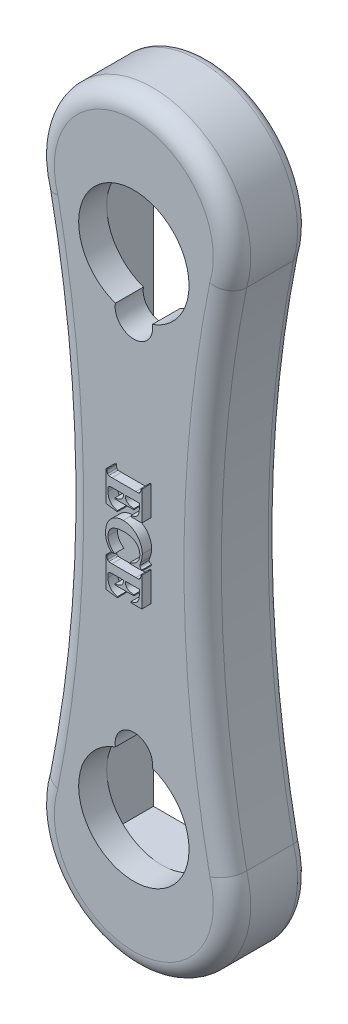
SolidWorks part; units mm, degrees
ref_plane "Front Plane" through (0, 0, 0) normal (0, 0, 1) x (1, 0, 0)
ref_plane "Top Plane" through (0, 0, 0) normal (0, 1, 0) x (1, 0, 0)
ref_plane "Right Plane" through (0, 0, 0) normal (1, 0, 0) x (0, 0, -1)
sketch "Sketch1" plane through (0, 0, 0) normal (0, 0, 1) x (1, 0, 0)
  line L0 (0, 60) -> (0, 0) construction
  circle A0 centre (0, 0) radius 10.5
  circle A1 centre (0, 60) radius 10.5
  arc A2 (-10.0623, 57) -> (-10.0623, 3) centre (-143.3775, 30) cw
  arc A3 (10.0623, 57) -> (10.0623, 3) centre (143.3775, 30) ccw
  point P3 (-7.5, 30)
  point P13 (7.5, 30)
  dimension "D1" = 21
  dimension "D2" = 21
  dimension "D3" = 60
  dimension "D4" = 7.5
  dimension "D5" = 3
  dimension "D6" = 3
extrude "Boss-Extrude1" add sketch "Sketch1" along normal blind 8 contours A1 | A0 | L0 A1 A2 A0 | A1 L0 A0 A3 region at (4.2043, 30, 0) region at (-4.2043, 30, 0) region at (-6.0975, 51.8194, 0) region at (6.0975, 8.1806, 0)
sketch "Sketch2" plane through (0, 0, 8) normal (0, 0, 1) x (1, 0, 0)
  line L0 (-7.3557, 30) -> (7.3557, 30) construction
  line L1 (-5.9007, 21) -> (5.8993, 21)
  line L2 (-5.9007, 62) -> (5.8993, 62)
  line L3 (-5.9007, 62) -> (-5.9007, 39)
  line L4 (-5.9007, 39) -> (5.8993, 39)
  line L5 (5.8993, 62) -> (5.8993, 39)
  line L6 (-5.9007, 62) -> (5.8993, 39) construction
  line L7 (-5.9007, 39) -> (5.8993, 62) construction
  line L8 (5.8993, -2) -> (5.8993, 21)
  line L9 (-5.9007, -2) -> (5.8993, -2)
  line L10 (-5.9007, -2) -> (-5.9007, 21)
  arc A0 (-10.0623, 3) -> (-10.0623, 57) centre (-143.3775, 30) ccw construction
  arc A1 (10.0623, 57) -> (10.0623, 3) centre (143.3775, 30) ccw construction
  arc A2 (10.0623, 57) -> (-10.0623, 57) centre (0, 60) ccw construction
  point P8 (-0.0007, 50.5)
  point P20 (0, 70.5)
  dimension "D1" = 11.8
  dimension "D2" = 1.455
  dimension "D3" = 23
  dimension "D4" = 8.5
extrude "Cut-Extrude1" cut sketch "Sketch2" against normal blind 6 from offset 3 offset against normal yes
sketch "Sketch4" plane through (0, 0, 5) normal (0, 0, -1) x (-1, 0, 0)
  line L0 (-5.8993, 62) -> (5.9007, 62) construction
  line L1 (5.9007, 62) -> (5.9007, 39) construction
  line L2 (-5.8993, 39) -> (-5.8993, 62) construction
  line L3 (-7.3557, 30) -> (7.3557, 30) construction
  arc A0 (1.9717, 50.539) -> (-1.9704, 50.539) centre (0.0007, 56.1) ccw
  arc A1 (-1.9704, 50.539) -> (1.9717, 50.539) centre (0.0007, 50.2) ccw
  arc A2 (-10.0623, 3) -> (-10.0623, 57) centre (-143.3775, 30) ccw construction
  arc A3 (10.0623, 57) -> (10.0623, 3) centre (143.3775, 30) ccw construction
  arc A4 (1.9717, 9.461) -> (-1.9704, 9.461) centre (0.0007, 3.9) cw
  arc A5 (-1.9704, 9.461) -> (1.9717, 9.461) centre (0.0007, 9.8) cw
  dimension "D1" = 4
extrude "Cut-Extrude2" cut sketch "Sketch4" against normal blind 3
sketch "Sketch5" plane through (0, 0, 0) normal (0, 0, -1) x (-1, 0, 0)
  line L0 (-5.8993, 62) -> (5.9007, 62) construction
  line L1 (5.9007, 39) -> (-5.8993, 39) construction
  line L2 (-7.3557, 30) -> (7.3557, 30) construction
  circle A0 centre (0.0007, 36.75) radius 0.75
  circle A1 centre (0.0007, 64.25) radius 0.75
  arc A2 (-10.0623, 3) -> (-10.0623, 57) centre (-143.3775, 30) ccw construction
  arc A3 (10.0623, 57) -> (10.0623, 3) centre (143.3775, 30) ccw construction
  circle A4 centre (0.0007, -4.25) radius 0.75
  circle A5 centre (0.0007, 23.25) radius 0.75
  point P12 (0.0007, 39)
  dimension "D1" = 1.5
  dimension "D2" = 1.5
  dimension "D3" = 2.25
  dimension "2.25" = 2.25
extrude "Cut-Extrude3" cut sketch "Sketch5" against normal blind 2
fillet "Fillet1" radius 2 4 edges at (0, -10.5, 8) (-7.3557, 30, 8) (0, 70.5, 8) (7.3557, 30, 8)
fillet "Fillet2" radius 1 4 edges at (7.3557, 30, 0) (0, -10.5, 0) (-7.3557, 30, 0) (0, 70.5, 0)
sketch "Sketch14" plane through (0, 0, 8) normal (0, 0, 1) x (1, 0, 0)
  line L0 (-1.9717, 50.539) -> (-1.9717, 9.461) construction
  text T0 "ECE" font "Times New Roman" height in points 16
extrude "Boss-Extrude2" add sketch "Sketch14" along normal blind 1
